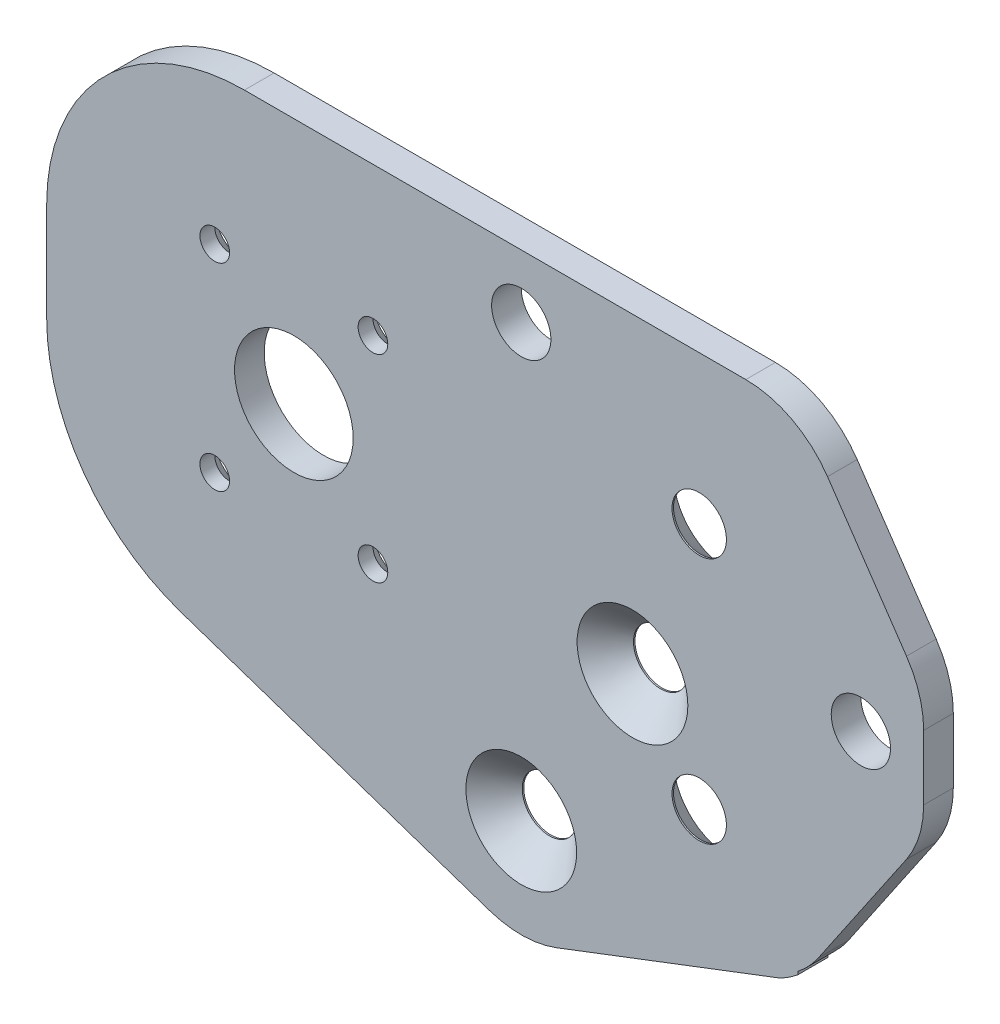
SolidWorks part; units mm, degrees
material "Gerais  - 6061-T6"
ref_plane "Plano frontal" through (0, 0, 0) normal (0, 0, 1) x (1, 0, 0)
ref_plane "Plano superior" through (0, 0, 0) normal (0, 1, 0) x (1, 0, 0)
ref_plane "Plano direito" through (0, 0, 0) normal (1, 0, 0) x (0, 0, -1)
sketch "Esboço1" plane through (0, 0, 0) normal (0, 0, 1) x (1, 0, 0)
  line L0 (56, 50) -> (56, 0) construction
  line L1 (0, 0) -> (76, 0)
  line L2 (0, 0) -> (0, 50)
  line L3 (0, 50) -> (76, 50)
  line L4 (76, 0) -> (76, 50)
  line L5 (66, 50) -> (66, 18.5) construction
  line L6 (65.25, 50) -> (65.25, 18.5) construction
  line L7 (59.25, 12.5) -> (25, 12.5) construction
  circle A0 centre (25, 25) radius 16 construction
  circle A1 centre (59.25, 18.5) radius 9.75 construction
  circle A2 centre (59.25, 18.5) radius 6 construction
  circle A3 centre (25, 25) radius 12.5 construction
  circle A4 centre (59.25, 18.5) radius 2.5
  circle A5 centre (25, 25) radius 6
  circle A6 centre (17, 38.8564) radius 1.5 construction
  circle A7 centre (33, 38.8564) radius 1.5 construction
  circle A8 centre (41, 25) radius 1.5 construction
  circle A9 centre (33, 11.1436) radius 1.5 construction
  circle A10 centre (17, 11.1436) radius 1.5 construction
  circle A11 centre (9, 25) radius 1.5 construction
  point P7 (41, 25)
  point P36 (25, 25)
  dimension "D1" = 32
  dimension "D5" = 12
  dimension "D6" = 19.5
  dimension "D9" = 25
  dimension "D10" = 5
  dimension "D13" = 12
  dimension "D14" = 3
  dimension "D2" = 25
  dimension "D3" = 35
  dimension "D4" = 20
  dimension "D7" = 0.75
  dimension "D8" = 10
  dimension "D11" = 25
  dimension "D12" = 50
  dimension "D15" = 6
extrude "Ressalto-extrusão1" add sketch "Esboço1" along normal blind 3
sketch "Esboço2" plane through (0, 0, 3) normal (0, 0, 1) x (1, 0, 0)
  line L0 (66, 50) -> (66, 0) construction
  line L1 (76, 50) -> (0, 50) construction
  line L2 (0, 0) -> (76, 0) construction
  line L3 (76, 0) -> (76, 50) construction
  circle A0 centre (66, 35) radius 2.5
  circle A1 centre (66, 10) radius 2.5
  dimension "D2" = 5
  dimension "D3" = 5
  dimension "D1" = 10
  dimension "D4" = 10
  dimension "D5" = 15
extrude "Corte-extrusão1" cut sketch "Esboço2" against normal blind 3
fillet "Filete1" radius 20 2 edges at (0, 0, 1.5) (0, 50, 1.5)
sketch "Esboço3" plane through (0, 0, 3) normal (0, 0, 1) x (1, 0, 0)
  line L1 (17, 15) -> (33, 15) construction
  line L2 (17, 15) -> (17, 35) construction
  line L3 (17, 35) -> (33, 35) construction
  line L4 (33, 15) -> (33, 35) construction
  line L5 (17, 15) -> (33, 35) construction
  line L6 (17, 35) -> (33, 15) construction
  circle A0 centre (33, 35) radius 1.5
  circle A1 centre (33, 15) radius 1.5
  circle A2 centre (17, 15) radius 1.5
  circle A3 centre (17, 35) radius 1.5
  point P0 (25, 25)
  dimension "D3" = 3
  dimension "D1" = 20
  dimension "D2" = 16
extrude "Corte-extrusão2" cut sketch "Esboço3" against normal through all
sketch "Esboço4" plane through (0, 0, 3) normal (0, 0, 1) x (1, 0, 0)
  line L0 (76, 50) -> (20, 50) construction
  line L1 (55.3323, 43.65) -> (51.6662, 50) construction
  line L2 (51.6662, 50) -> (44.3338, 50) construction
  line L3 (44.3338, 50) -> (40.6677, 43.65) construction
  line L4 (40.6677, 43.65) -> (44.3338, 37.3) construction
  line L5 (44.3338, 37.3) -> (51.6662, 37.3) construction
  line L6 (51.6662, 37.3) -> (55.3323, 43.65) construction
  line L7 (76, 0) -> (76, 50) construction
  line L9 (51.4498, -6.4701) -> (55.3282, -0.2474) construction
  line L10 (55.3282, -0.2474) -> (51.8783, 6.2227) construction
  line L11 (51.8783, 6.2227) -> (44.5502, 6.4701) construction
  line L12 (44.5502, 6.4701) -> (40.6718, 0.2474) construction
  line L13 (40.6718, 0.2474) -> (44.1217, -6.2227) construction
  line L14 (44.1217, -6.2227) -> (51.4498, -6.4701) construction
  line L15 (25, 12.5) -> (61.6574, 12.5) construction
  line L16 (20, 0) -> (76, 0) construction
  line L17 (48, 43.65) -> (48, 0) construction
  circle A0 centre (48, 43.65) radius 3
  circle A1 centre (48, 43.65) radius 6.35 construction
  circle A2 centre (48, 0) radius 2.5
  circle A3 centre (48, 0) radius 6.35 construction
  arc A4 (17.8926, 14.7172) -> (30.3514, 13.7035) centre (25, 25) ccw construction
  arc A5 (17.8926, 14.7172) -> (30.3514, 13.7035) centre (25, 25) ccw construction
  dimension "D1" = 12.7
  dimension "D3" = 6
  dimension "D4" = 5
  dimension "D2" = 28
extrude "Corte-extrusão3" cut sketch "Esboço4" against normal through all
sketch "Esboço5" plane through (0, 0, 0) normal (0, 0, -1) x (-1, 0, 0)
  line L0 (-76, 0) -> (-51.5714, -9.3405)
  line L1 (-44.8034, -9.4753) -> (-13.6067, 1.0494)
  line L2 (-20, 0) -> (-45.5, 0) construction
  line L3 (-50.5, 0) -> (-76, 0) construction
  line L4 (-20, 0) -> (-45.5, 0)
  line L5 (-50.5, 0) -> (-76, 0)
  circle A0 centre (-48, 0) radius 2.5
  arc A1 (-51.5714, -9.3405) -> (-44.8034, -9.4753) centre (-48, 0) ccw
  arc A2 (-20, 0) -> (0, 20) centre (-20, 20) ccw construction
  line M5 (-45.5, 0) -> (-20, 0)
  arc M6 (-20, 0) -> (0, 20) centre (-20, 20) ccw
  line M11 (-76, 0) -> (-50.5, 0)
  dimension "D1" = 20
extrude "Ressalto-extrusão2" add sketch "Esboço5" against normal through all contours L0 A1 L1 A0 M6 M5 M11 region at (46.8798, -3.5834, 0)
sketch "Esboço6" plane through (0, 0, 0) normal (0, 0, -1) x (-1, 0, 0)
  line L7 (-86.9656, 16.103) -> (-78.0603, 3.0256)
  line L8 (-72.4733, -0.9805) -> (-50.0089, -7.2259)
  line L9 (-46.1556, -7.2697) -> (-15.0816, 0.6142)
  line L10 (0, 20) -> (0, 30)
  line L11 (-20, 50) -> (-70.7112, 50)
  line L12 (-78.9768, 45.6286) -> (-86.9656, 33.897)
  line L13 (-88.7, 28.2685) -> (-88.7, 21.7315)
  line L14 (-86.9656, 16.103) -> (-78.0603, 3.0256)
  line L15 (-72.4733, -0.9805) -> (-50.0089, -7.2259)
  line L16 (-46.1556, -7.2697) -> (-15.0816, 0.6142)
  line L17 (0, 20) -> (0, 30)
  line L18 (-20, 50) -> (-70.7112, 50)
  line L19 (-78.9768, 45.6286) -> (-86.9656, 33.897)
  line L20 (-88.7, 28.2685) -> (-88.7, 21.7315)
  circle A0 centre (-82.35, 25) radius 3 construction
  circle A1 centre (-82.35, 25) radius 3
  arc A7 (-78.0603, 3.0256) -> (-72.4733, -0.9805) centre (-69.7947, 8.6541) ccw
  arc A8 (-50.0089, -7.2259) -> (-46.1556, -7.2697) centre (-48, 0) ccw
  arc A9 (-15.0816, 0.6142) -> (0, 20) centre (-20, 20) ccw
  arc A10 (0, 30) -> (-20, 50) centre (-20, 30) ccw
  arc A11 (-70.7112, 50) -> (-78.9768, 45.6286) centre (-70.7112, 40) ccw
  arc A12 (-86.9656, 33.897) -> (-88.7, 28.2685) centre (-78.7, 28.2685) ccw
  arc A13 (-88.7, 21.7315) -> (-86.9656, 16.103) centre (-78.7, 21.7315) ccw
  arc A15 (-50.0089, -7.2259) -> (-46.1556, -7.2697) centre (-48, 0) ccw
  arc A16 (-15.0816, 0.6142) -> (0, 20) centre (-20, 20) ccw
  arc A17 (0, 30) -> (-20, 50) centre (-20, 30) ccw
  arc A18 (-70.7112, 50) -> (-78.9768, 45.6286) centre (-70.7112, 40) ccw
  arc A19 (-86.9656, 33.897) -> (-88.7, 28.2685) centre (-78.7, 28.2685) ccw
  arc A20 (-88.7, 21.7315) -> (-86.9656, 16.103) centre (-78.7, 21.7315) ccw
  arc A54 (-78.0603, 3.0256) -> (-72.4733, -0.9805) centre (-69.7947, 8.6541) ccw
  line M16 (-76, 50) -> (-76, 0)
  dimension "D1" = 0
extrude "Ressalto-extrusão3" add sketch "Esboço6" against normal through all contours L20 A20 L14 A54 A18 L19 A19 A1 M16 region at (87.7851, 18.9319, 0)
sketch "Esboço7" plane through (0, 0, 0) normal (0, 0, -1) x (-1, 0, 0)
  line L0 (-76, 0) -> (-51.5714, -9.3405) construction
  line L9 (-76, 0.8122) -> (-76, 0)
  line L10 (-76, 0) -> (-51.5714, -9.3405)
  line L11 (-44.8034, -9.4753) -> (-13.6067, 1.0494)
  line L12 (0, 20) -> (0, 30)
  line L13 (-20, 50) -> (-76, 50)
  line L15 (-78.9768, 45.6286) -> (-86.9656, 33.897)
  line L16 (-88.7, 28.2685) -> (-88.7, 21.7315)
  line L17 (-86.9656, 16.103) -> (-78.0603, 3.0256)
  line L18 (-76, 0.8122) -> (-76, 0)
  line L19 (-76, 0) -> (-51.5714, -9.3405)
  line L20 (-44.8034, -9.4753) -> (-13.6067, 1.0494)
  line L21 (0, 20) -> (0, 30)
  line L22 (-20, 50) -> (-76, 50)
  line L24 (-78.9768, 45.6286) -> (-86.9656, 33.897)
  line L25 (-88.7, 28.2685) -> (-88.7, 21.7315)
  line L26 (-86.9656, 16.103) -> (-78.0603, 3.0256)
  line L27 (-76, 50) -> (-76, 48.487)
  line L28 (-76, 50) -> (-76, 48.487)
  arc A0 (-78.9768, 45.6286) -> (-70.7112, 50) centre (-70.7112, 40) cw
  arc A1 (-78.0603, 3.0256) -> (-72.5961, -1.3015) centre (-70.1034, 7.4599) ccw
  arc A7 (-51.5714, -9.3405) -> (-44.8034, -9.4753) centre (-48, 0) ccw
  arc A8 (-13.6067, 1.0494) -> (0, 20) centre (-20, 20) ccw
  arc A9 (0, 30) -> (-20, 50) centre (-20, 30) ccw
  arc A10 (-76, 48.487) -> (-78.9768, 45.6286) centre (-70.7112, 40) ccw
  arc A11 (-86.9656, 33.897) -> (-88.7, 28.2685) centre (-78.7, 28.2685) ccw
  arc A12 (-88.7, 21.7315) -> (-86.9656, 16.103) centre (-78.7, 21.7315) ccw
  arc A14 (-51.5714, -9.3405) -> (-44.8034, -9.4753) centre (-48, 0) ccw
  arc A15 (-13.6067, 1.0494) -> (0, 20) centre (-20, 20) ccw
  arc A16 (0, 30) -> (-20, 50) centre (-20, 30) ccw
  arc A17 (-76, 48.487) -> (-78.9768, 45.6286) centre (-70.7112, 40) ccw
  arc A18 (-86.9656, 33.897) -> (-88.7, 28.2685) centre (-78.7, 28.2685) ccw
  arc A19 (-88.7, 21.7315) -> (-86.9656, 16.103) centre (-78.7, 21.7315) ccw
  arc A22 (-78.0603, 3.0256) -> (-76, 0.8122) centre (-69.7947, 8.6541) ccw
  arc A23 (-78.0603, 3.0256) -> (-76, 0.8122) centre (-69.7947, 8.6541) ccw
  line M18 (-76, 0.8122) -> (-76, 0)
  line M19 (-76, 0) -> (-51.5714, -9.3405)
  line M26 (-76, 50) -> (-76, 48.487)
  dimension "D1" = 0
extrude "Corte-extrusão4" cut sketch "Esboço7" against normal through all contours A1 M18 M19 | A0 L22 M26 region at (75.4496, -0.0541, 0) region at (74.6987, 49.5527, 0)
chamfer "Chanfro1" distance 1.5 angle 45 4 edges at (18.5, 35, 0) (18.5, 15, 0) (34.5, 15, 0) (34.5, 35, 0)
hole_wizard "Escareado para SFHCS M51" positions "Esboço16" profile "Esboço17" countersink size "M5" standard "Ansi Metric" end condition through all
sketch "Esboço16" plane through (0, 0, 3) normal (0, 0, 1) x (1, 0, 0)
  point P0 (48, 0)
sketch "Esboço17" plane through (48, 0, 3) normal (1, 0, 0) x (0, -1, 0)
  line L0 (0, 0) -> (0, 3)
  line L1 (0, 3) -> (2.75, 3)
  line L2 (2.75, 3) -> (2.75, 2.85)
  line L3 (2.75, 2.85) -> (5.6, 0)
  line L5 (5.6, 0) -> (0, 0)
  line L6 (-2.75, 2.85) -> (-5.6, 0) construction
  line L11 (0, -6.35) -> (0, 107.95) construction
  dimension "Thru Hole Dia." = 5.5
  dimension "Thru Hole Depth" = 3
  dimension "Near C'Sink Dia." = 11.2
  dimension "Near C'Sink Angle" = 90
hole_wizard "Escareado para SFHCS M52" positions "Esboço18" profile "Esboço19" countersink size "M5" standard "Ansi Metric" end condition through all
sketch "Esboço18" plane through (0, 0, 3) normal (0, 0, 1) x (1, 0, 0)
  point P0 (59.25, 18.5)
sketch "Esboço19" plane through (59.25, 18.5, 3) normal (1, 0, 0) x (0, -1, 0)
  line L0 (0, 0) -> (0, 3)
  line L1 (0, 3) -> (2.75, 3)
  line L2 (2.75, 3) -> (2.75, 2.85)
  line L3 (2.75, 2.85) -> (5.6, 0)
  line L5 (5.6, 0) -> (0, 0)
  line L6 (-2.75, 2.85) -> (-5.6, 0) construction
  line L11 (0, -6.35) -> (0, 107.95) construction
  dimension "Thru Hole Dia." = 5.5
  dimension "Thru Hole Depth" = 3
  dimension "Near C'Sink Dia." = 11.2
  dimension "Near C'Sink Angle" = 90
hole_wizard "Escareado para SFHCS M54" positions "Esboço22" profile "Esboço23" countersink size "M5" standard "Ansi Metric" end condition through all
sketch "Esboço22" plane through (0, 0, 0) normal (0, 0, -1) x (-1, 0, 0)
  point P0 (-66, 35)
  point P3 (-66, 10)
sketch "Esboço23" plane through (66, 35, 0) normal (1, 0, 0) x (0, 1, 0)
  line L0 (0, 0) -> (0, 3)
  line L1 (0, 3) -> (2.75, 3)
  line L2 (2.75, 3) -> (2.75, 2.85)
  line L3 (2.75, 2.85) -> (5.6, 0)
  line L5 (5.6, 0) -> (0, 0)
  line L6 (-2.75, 2.85) -> (-5.6, 0) construction
  line L11 (0, -6.35) -> (0, 107.95) construction
  dimension "Thru Hole Dia." = 5.5
  dimension "Thru Hole Depth" = 3
  dimension "Near C'Sink Dia." = 11.2
  dimension "Near C'Sink Angle" = 90
